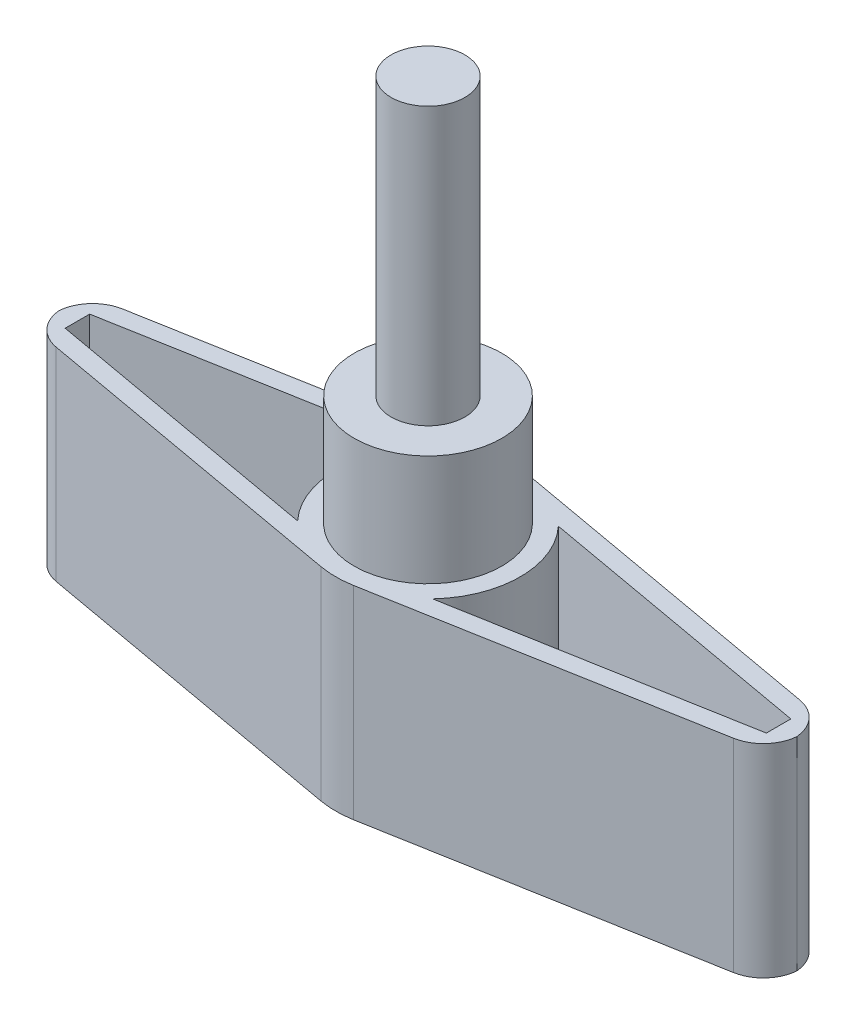
SolidWorks part; units mm, degrees
material "Rubber"
ref_plane "Front Plane" through (0, 0, 0) normal (0, 0, 1) x (1, 0, 0)
ref_plane "Top Plane" through (0, 0, 0) normal (0, 1, 0) x (1, 0, 0)
ref_plane "Right Plane" through (0, 0, 0) normal (1, 0, 0) x (0, 0, -1)
sketch "Sketch1" plane through (0, 0, 0) normal (0, 1, 0) x (1, 0, 0)
  line L1 (-20.0002, 1.5009) -> (-20.0002, -1.5009)
  line L2 (-20.0002, 1.5009) -> (-0.8806, 4.9218)
  line L3 (-20.0002, -1.5009) -> (-0.8806, -4.9218)
  line L4 (-19.0002, -0.6639) -> (-19.0002, 0.6639)
  line L5 (-18.824, -0.6954) -> (-19.0002, -0.6639)
  line L6 (-18.824, 0.6954) -> (-3.6576, 3.4091)
  line L7 (-18.824, 0.6954) -> (-19.0002, 0.6639)
  line L8 (-18.824, -0.6954) -> (-3.6576, -3.4091)
  line L10 (18.824, 0.6954) -> (19.0002, 0.6639)
  line L11 (18.824, 0.6954) -> (3.6576, 3.4091)
  line L12 (18.824, -0.6954) -> (19.0002, -0.6639)
  line L13 (19.0002, -0.6639) -> (19.0002, 0.6639)
  line L14 (20.0002, -1.5009) -> (0.8806, -4.9218)
  line L15 (20.0002, 1.5009) -> (0.8806, 4.9218)
  line L16 (20.0002, 1.5009) -> (20.0002, -1.5009)
  line L18 (18.824, -0.6954) -> (3.6576, -3.4091)
  arc A2 (-3.6576, 3.4091) -> (-3.6576, -3.4091) centre (0, 0) ccw
  arc A3 (0.8806, 4.9218) -> (-0.8806, 4.9218) centre (0, 0) ccw
  arc A4 (3.6576, -3.4091) -> (3.6576, 3.4091) centre (0, 0) ccw
  arc A5 (-0.8806, -4.9218) -> (0.8806, -4.9218) centre (0, 0) ccw
  point P7 (-20.0002, 0)
  point P29 (20.0002, 0)
extrude "Boss-Extrude1" add sketch "Sketch1" along normal blind 10
sketch "Sketch2" plane through (0, 0, 0) normal (0, -1, 0) x (1, 0, 0)
  line L0 (-20.0002, 1.5009) -> (-0.8806, 4.9218)
  line L1 (-20.0002, 1.5009) -> (-20.0002, -1.5009)
  line L2 (20.0002, 1.5009) -> (20.0002, -1.5009)
  line L3 (-20.0002, -1.5009) -> (-0.8806, -4.9218)
  line L4 (0.8806, -4.9218) -> (20.0002, -1.5009)
  line L5 (20.0002, 1.5009) -> (0.8806, 4.9218)
  arc A1 (-0.8806, -4.9218) -> (0.8806, -4.9218) centre (0, 0) ccw
  arc A2 (0.8806, 4.9218) -> (-0.8806, 4.9218) centre (0, 0) ccw
extrude "Boss-Extrude2" add sketch "Sketch2" along normal blind 1
sketch "Sketch3" plane through (0, 10, 0) normal (0, 1, 0) x (1, 0, 0)
  circle A0 centre (0, 0) radius 4
extrude "Boss-Extrude3" add sketch "Sketch3" along normal blind 6
sketch "Sketch4" plane through (0, 16, 0) normal (0, 1, 0) x (1, 0, 0)
  circle A0 centre (0, 0) radius 2
extrude "Boss-Extrude4" add sketch "Sketch4" along normal blind 15
cosmetic thread "Cosmetic Thread1" parameters "D2"=2
fillet "Fillet1" radius 2 4 edges at (20.0002, 4.5, 1.5009) (20.0002, 4.5, -1.5009) (-20.0002, 4.5, -1.5009) (-20.0002, 4.5, 1.5009)
